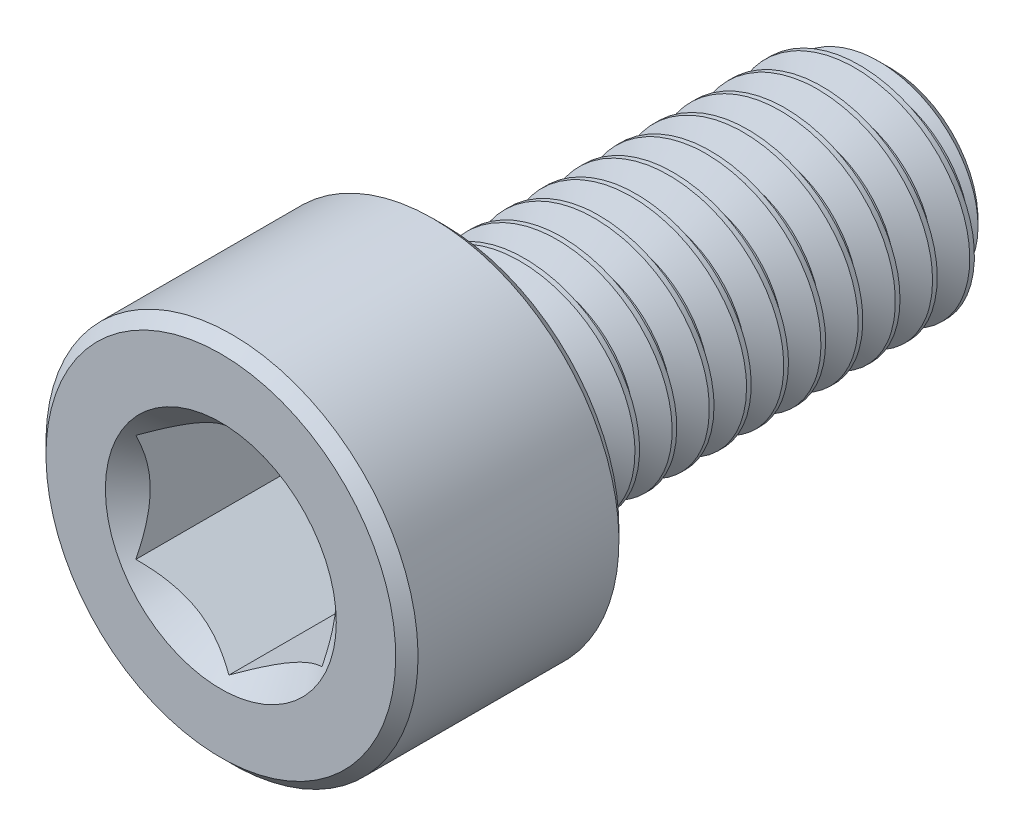
SolidWorks part; units mm, degrees
ref_plane "Front Plane" through (0, 0, 0) normal (0, 0, 1) x (1, 0, 0)
ref_plane "Top Plane" through (0, 0, 0) normal (0, 1, 0) x (1, 0, 0)
ref_plane "Right Plane" through (0, 0, 0) normal (1, 0, 0) x (0, 0, -1)
sketch "Sketch1" plane through (0, 0, 0) normal (1, 0, 0) x (0, 0, -1)
  line L0 (-9, 0) -> (9, 0) construction
  line L1 (9, 0) -> (9, 2.3505) construction
  line L2 (9, 2.3505) -> (8.3505, 3) construction
  line L3 (8.3505, 3) -> (8.25, 3) construction
  line L4 (8.25, 3) -> (-3, 3) construction
  line L5 (-3, 3) -> (-3, 5) construction
  line L6 (-3, 5) -> (-9, 5) construction
  line L7 (-9, 5) -> (-9, 0) construction
  line L8 (9, 2.3505) -> (9, 3) construction
  line L9 (8.9375, 3.1083) -> (9.4375, 2.2422) construction
  line L10 (9.4375, 2.2422) -> (9.9375, 3.1083) construction
  line L11 (9.9375, 3.1083) -> (8.9375, 3.1083) construction
  line L12 (9.4375, 3.1083) -> (9.4375, 3) construction
  line L13 (9.4375, 2.2422) -> (9.4375, 2.3505) construction
  line L14 (9.375, 2.3505) -> (9.5, 2.3505) construction
  line L15 (9, 3) -> (9.875, 3) construction
  line L16 (8.9688, 3.0541) -> (9.9062, 3.0541) construction
  line L17 (9, 0) -> (9, -3) construction
  line L18 (-3.3, 5) -> (-3, 4.7) construction
  line L19 (-8.7, 5) -> (-9, 4.7) construction
  line L20 (-3, 3) -> (-3, 0) construction
  line L21 (-3, 1.5) -> (1, 1.5) construction
  line L22 (1, 1.5) -> (5, 1.5) construction
  line L23 (5, 1.5) -> (9, 1.5) construction
  line L24 (1, 1.5) -> (1, 3) construction
  line L25 (1, 3) -> (1, 5) construction
  line L26 (5, 1.5) -> (5, 5) construction
  point P0 (-9, 2.5)
  point P3 (6.5, 3)
  point P4 (0, 0)
  point P18 (5, 3)
  point P22 (9.4375, 2.3505)
  point P24 (8.25, 3)
  point P25 (9.4375, 3)
  point P28 (9.4375, 3.0541)
  point P29 (6.5, -3)
  point P30 (1, 3)
  point P31 (-6, 5)
  point P37 (-4.05, 5)
  point P38 (-8.55, 5)
  point P45 (1, 1.5)
  point P46 (5, 1.5)
  dimension "D2" = 0.125
  dimension "D7" = 0.3
  dimension "D8" = 0.3
  dimension "D9" = 0.3
  dimension "D10" = 0.15
  dimension "D11" = 0.75
  dimension "Drive Size" = 5
  dimension "Head Diameter" = 10
  dimension "Head Height" = 6
  dimension "Thread Pitch" = 1
  dimension "Thread Dia" = 6
  dimension "Length" = 12
  dimension "D12" = 0.75
  dimension "D4" = 2.5
  dimension "D3" = 45
sketch "Sketch2" plane through (0, 0, 0) normal (1, 0, 0) x (0, 0, -1)
  line L0 (-9, 0) -> (-9, 4.7)
  line L1 (-8.7, 5) -> (-3.3, 5)
  line L2 (-3, 4.7) -> (-3, 3.3)
  line L4 (8.3505, 3) -> (9, 2.3505)
  line L5 (9, 2.3505) -> (9, 0)
  line L6 (-3, 5) -> (-9, 5) construction
  line L7 (9, 0) -> (-9, 0)
  line L8 (-8.7, 5) -> (-9, 4.7) construction
  line L10 (-8.7, 5) -> (-9, 4.7)
  line L14 (-3.3, 5) -> (-3, 4.7) construction
  line L16 (-3.3, 5) -> (-3, 4.7)
  line L17 (-3, 3) -> (-3, 5) construction
  line L19 (-2.7, 3) -> (8.3505, 3)
  line L20 (8.25, 3) -> (-3, 3) construction
  arc A1 (-3, 3.3) -> (-2.7, 3) centre (-2.7, 3.3) ccw
  dimension "D3" = 0.3
revolve "Revolve1" add sketch "Sketch2" angle 360 about L7
sketch "Sketch3" plane through (0, 0, 9) normal (0, 0, 1) x (1, 0, 0)
  line L1 (2.5, -1.4434) -> (2.5, 1.4434)
  line L2 (2.5, 1.4434) -> (0, 2.8868)
  line L3 (0, 2.8868) -> (-2.5, 1.4434)
  line L4 (-2.5, 1.4434) -> (-2.5, -1.4434)
  line L5 (-2.5, -1.4434) -> (0, -2.8868)
  line L6 (0, -2.8868) -> (2.5, -1.4434)
  circle A0 centre (0, 0) radius 2.5 construction
  circle A1 centre (0, 0) radius 5 construction
  circle A2 centre (0, 0) radius 5 construction
  circle A3 centre (0, 0) radius 2.8868 construction
  point P13 (0, 0)
  dimension "D1" = 5.7735
extrude "Cut-Extrude1" cut sketch "Sketch3" against normal offset from surface (5 mm away) 1 up to face at (0, 4.7, 3)
sketch "Sketch4" plane through (0, 0, 9) normal (0, 0, 1) x (1, 0, 0)
  circle A0 centre (0, 0) radius 3.1033
  dimension "D1" = 6.2065
extrude "Cut-Extrude2" cut sketch "Sketch4" against normal up to vertex (3 mm away) draft 45 up to point (0, 5, 6)
sketch "Sketch11" plane through (0, 0, 0) normal (1, 0, 0) x (0, 0, -1)
  line L0 (-9, 0) -> (9, 0) construction
  line L1 (-9, 0) -> (9, 0) construction
  line L2 (-0.75, 0) -> (-0.75, 3) construction
  line L3 (8.25, 3) -> (-3, 3) construction
  line L4 (6.75, 0) -> (6.75, 3) construction
  line L6 (9, 2.3505) -> (9, 3) construction
  point P2 (-0.75, 0)
  point P3 (6.75, 0)
  dimension "D1" = 2.25
  dimension "D2" = 2.25
sketch "Sketch6" plane through (0, 0, -9) normal (0, 0, -1) x (-1, 0, 0)
  circle A0 centre (0, 0) radius 3
curve "Helix/Spiral1" pitch 1 height 13 turns 13
sketch "Sketch10" plane through (0, 0, 0) normal (1, 0, 0) x (0, 0, -1)
  line L0 (-2.7, -5) -> (-2.7, 5)
  line L5 (-9, 0) -> (9, 0) construction
  line L6 (-2.7, 3) -> (-2.7, -3) construction
  point P3 (-2.7, 0)
split "Split1" trim tools "Sketch10" bodies to split 106 resulting bodies 114 115
sketch "Sketch7" plane through (0, 0, 0) normal (1, 0, 0) x (0, 0, -1)
  line L0 (8.9688, 3.0541) -> (9.9062, 3.0541)
  line L1 (9.9062, 3.0541) -> (9.5, 2.3505)
  line L2 (9.5, 2.3505) -> (9.375, 2.3505)
  line L3 (9.375, 2.3505) -> (8.9688, 3.0541)
sweep "Cut-Sweep1" cut profiles "Sketch7" path "Helix/Spiral1" align with end faces yes
sketch "Sketch8" plane through (0, 0, 0) normal (1, 0, 0) x (0, 0, -1)
  line L0 (-3, 0) -> (-3, 3)
  line L1 (-2.7, -3) -> (-2.7, 3) construction
  line L2 (-3, 3) -> (-2.7, 3)
  line L4 (-2.7, 3) -> (-0.9679, 0)
  line L5 (-0.9679, 0) -> (-3, 0)
  line L6 (8.25, 3) -> (-3, 3) construction
  line L7 (-9, 0) -> (9, 0) construction
  dimension "D1" = 60
revolve "Revolve2" add sketch "Sketch8" angle 360 about L5
equation "\"D2@Sketch1\" = \"Thread Pitch@Sketch1\" / 8"
equation "\"D4@Helix/Spiral1\" = \"Thread Pitch@Sketch1\""
equation "\"D7@Sketch1\" = \"Head Height@Sketch1\" * .05"
equation "\"D8@Sketch1\"=\"D7@Sketch1\""
equation "\"D9@Sketch1\"=\"D7@Sketch1\""
equation "\"D10@Sketch1\"=\"D7@Sketch1\"/2"
equation "\"D11@Sketch1\"=\"D10@Sketch1\"*5"
equation "\"D4@Sketch1\"=\"Thread Pitch@Sketch1\"*2.5"
equation "\"D12@Sketch1\"=\"Thread Pitch@Sketch1\"*.75"
equation "\"D3@Helix/Spiral1\"=\"Length@Sketch1\"+\"Thread Pitch@Sketch1\""
equation "\"D3@Sketch2\"=\"Thread Dia@Sketch1\"*0.05"
equation "\"D1@Sketch11\"=\"Length@Sketch1\"*0.1875"
equation "\"D2@Sketch11\"=\"D1@Sketch11\""
equation "\"D1@Sketch4\"=\"D1@Sketch3\"*1.075"
